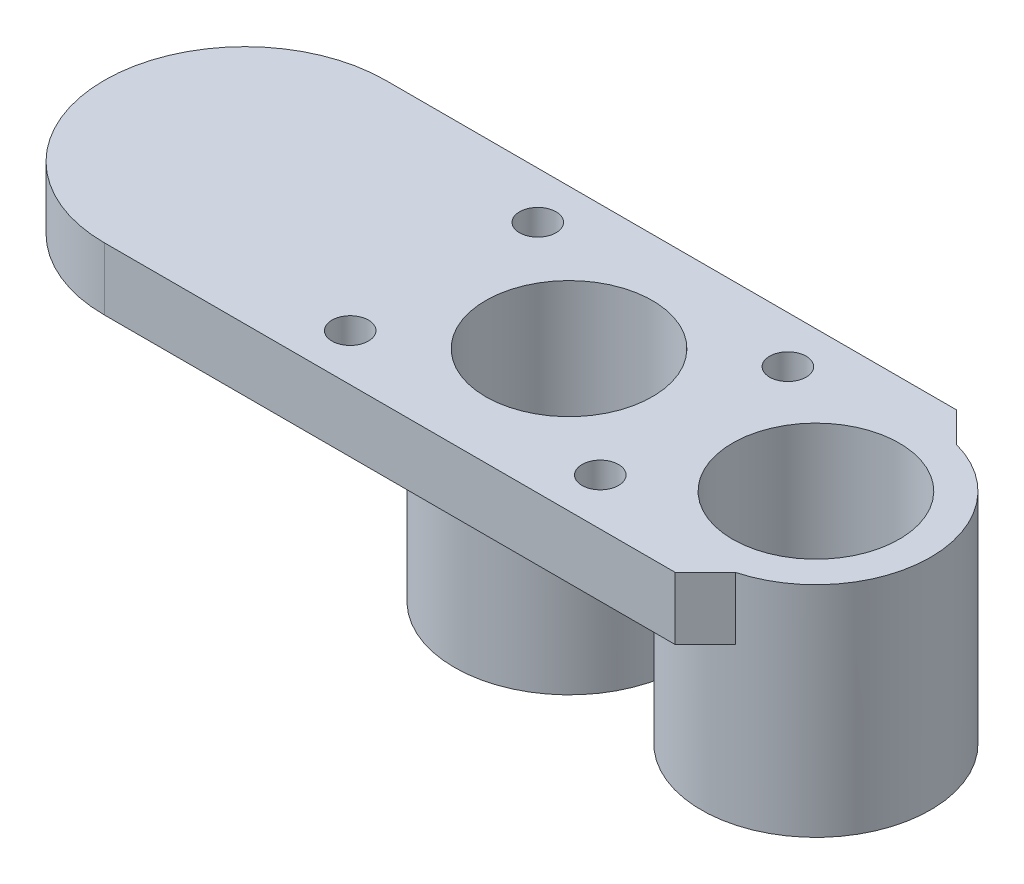
SolidWorks part; units mm, degrees
ref_plane "Front Plane" through (0, 0, 0) normal (0, 0, 1) x (1, 0, 0)
ref_plane "Top Plane" through (0, 0, 0) normal (0, 1, 0) x (1, 0, 0)
ref_plane "Right Plane" through (0, 0, 0) normal (1, 0, 0) x (0, 0, -1)
sketch "Sketch1" plane through (0, 0, 0) normal (0, 1, 0) x (1, 0, 0)
  line L1 (-31.1, 13.5) -> (23.69, 13.5)
  line L2 (-31.1, 13.5) -> (-31.1, -13.5)
  line L3 (-31.1, -13.5) -> (23.69, -13.5)
  line L4 (23.69, 13.5) -> (23.69, -13.5)
  circle A0 centre (23.69, 0) radius 11
  circle A1 centre (-31.1, 0) radius 10.5
  circle A2 centre (12, 9) radius 1.75
  circle A3 centre (23.69, 0) radius 5
  circle A4 centre (0, 0) radius 5
  circle A5 centre (12, -9) radius 1.75
  circle A6 centre (-12, -9) radius 1.75
  circle A7 centre (-12, 9) radius 1.75
  dimension "D5" = 22
  dimension "D6" = 21
  dimension "D7" = 3.5
  dimension "D10" = 10
  dimension "D11" = 10
  dimension "D12" = 3.5
  dimension "D15" = 3.5
  dimension "D17" = 3.5
  dimension "D1" = 31.1
  dimension "D2" = 23.69
  dimension "D3" = 27
  dimension "D4" = 13.5
  dimension "D8" = 12
  dimension "D9" = 9
  dimension "D13" = 12
  dimension "D14" = 9
  dimension "D16" = 12
extrude "Boss-Extrude1" add sketch "Sketch1" along normal blind 6 contours A1 L2 L3 L4 A0 L1 A7 A6 A5 A4 A2 | A3 L4 A0 | A3 L4 A0 region at (-3.705, 0, -12.8892) region at (29.0217, 0, 0) region at (18.3583, 0, 0)
sketch "Sketch2" plane through (0, 0, 0) normal (0, -1, 0) x (1, 0, 0)
  circle A0 centre (12, -9) radius 1.75 construction
  circle A1 centre (12, 9) radius 1.75 construction
  circle A2 centre (-12, 9) radius 1.75 construction
  circle A3 centre (-12, -9) radius 1.75 construction
  circle A4 centre (12, -9) radius 1.75
  circle A5 centre (12, 9) radius 1.75
  circle A6 centre (-12, 9) radius 1.75
  circle A7 centre (-12, -9) radius 1.75
  circle A8 centre (-12, -9) radius 3
  circle A9 centre (-12, 9) radius 3
  circle A10 centre (12, 9) radius 3
  circle A11 centre (12, -9) radius 3
  dimension "D1" = 6
  dimension "D2" = 6
  dimension "D3" = 6
  dimension "D4" = 6
extrude "Cut-Extrude1" cut sketch "Sketch2" against normal blind 3
sketch "Sketch3" plane through (0, 6, 0) normal (0, 1, 0) x (1, 0, 0)
  circle A0 centre (0, 0) radius 8
  circle A1 centre (0, 0) radius 5 construction
  circle A2 centre (23.69, 0) radius 5 construction
  circle A3 centre (0, 0) radius 5
  circle A4 centre (23.69, 0) radius 5
  circle A5 centre (23.69, 0) radius 8
  dimension "D1" = 16
  dimension "D2" = 16
extrude "Cut-Extrude2" cut sketch "Sketch3" against normal blind 3
sketch "Sketch5" plane through (0, 0, 0) normal (0, 1, 0) x (1, 0, 0)
  arc A0 (-31.1, -10.5) -> (-31.1, 10.5) centre (-31.1, 0) ccw construction
  arc A1 (-31.1, -10.5) -> (-31.1, 10.5) centre (-31.1, 0) ccw
  circle A2 centre (-31.1, 0) radius 13.5
extrude "Boss-Extrude2" add sketch "Sketch5" along normal blind 6 contours A2 region at (-31.1, 0, 0)
sketch "Sketch6" plane through (0, 6, 0) normal (0, 1, 0) x (1, 0, 0)
  arc A0 (23.69, -11) -> (23.69, 11) centre (23.69, 0) ccw construction
  circle A1 centre (23.69, 0) radius 8 construction
  circle A2 centre (0, 0) radius 8 construction
  arc A3 (23.69, -11) -> (23.69, 11) centre (23.69, 0) ccw
  circle A4 centre (23.69, 0) radius 8
  circle A5 centre (0, 0) radius 8
  circle A6 centre (0, 0) radius 11
  circle A7 centre (23.69, 0) radius 11
  circle M8 centre (0, 0) radius 8
  circle M9 centre (23.69, 0) radius 8
  dimension "D1" = 22
extrude "Cut-Extrude3" cut sketch "Sketch6" against normal through all both and the other way through all contours M8 | M9 region at (23.69, 6, 0) region at (0, 6, 0)
sketch "Sketch9" plane through (0, 0, 0) normal (0, 1, 0) x (1, 0, 0)
  arc A0 (23.69, -11) -> (23.69, 11) centre (23.69, 0) ccw construction
  circle A1 centre (23.69, 0) radius 8 construction
  circle A2 centre (0, 0) radius 8 construction
  arc A3 (23.69, -11) -> (23.69, 11) centre (23.69, 0) ccw
  circle A4 centre (23.69, 0) radius 8
  circle A5 centre (0, 0) radius 8
  circle A6 centre (0, 0) radius 11
  circle A7 centre (23.69, 0) radius 11
  dimension "D1" = 22
extrude "Boss-Extrude6" add sketch "Sketch9" against normal blind 12 contours A6 A5 | A3 A7 A4 region at (13.0011, 0, 0) region at (-10.6889, 0, 0)
sketch "Sketch10" plane through (0, -12, 0) normal (0, -1, 0) x (1, 0, 0)
  circle A0 centre (23.69, 0) radius 11 construction
  circle A1 centre (0, 0) radius 11 construction
  circle A2 centre (23.69, 0) radius 11
  circle A3 centre (0, 0) radius 11
  circle A4 centre (0, 0) radius 5
  circle A5 centre (23.69, 0) radius 5
  dimension "D1" = 10
  dimension "D2" = 10
extrude "Boss-Extrude7" add sketch "Sketch10" along normal blind 3
chamfer "Chamfer3" distance 2.5 angle 45 2 edges at (23.69, 3, 11) (23.69, 3, -11)
